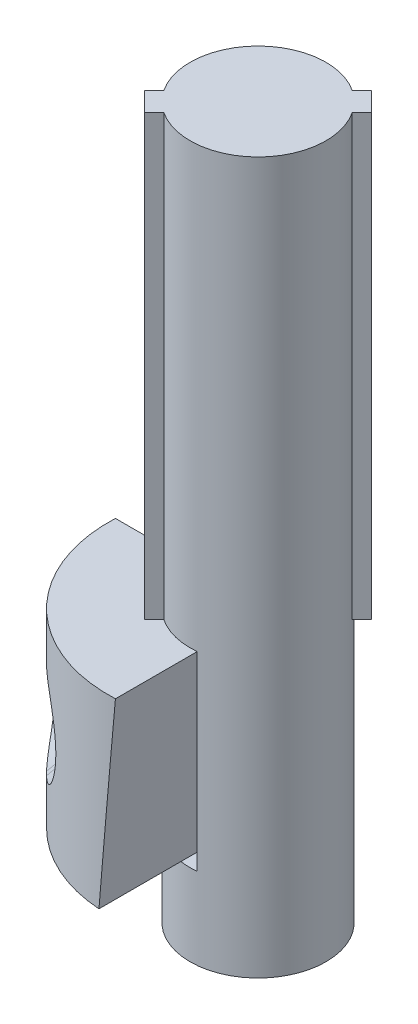
SolidWorks part; units mm, degrees
ref_plane "Front Plane" through (0, 0, 0) normal (0, 0, 1) x (1, 0, 0)
ref_plane "Top Plane" through (0, 0, 0) normal (0, 1, 0) x (1, 0, 0)
ref_plane "Right Plane" through (0, 0, 0) normal (1, 0, 0) x (0, 0, -1)
sketch "Sketch1" plane through (0, 0, 0) normal (0, 1, 0) x (1, 0, 0)
  line L0 (0, 12.1683) -> (0, -14.062) construction
  line L1 (-13.6994, 0) -> (17.366, 0) construction
  line L2 (0.0057, 5.75) -> (3.0125, 5.75)
  line L3 (5.75, 3.0125) -> (5.75, 0.0057)
  arc A0 (5.75, 0.0057) -> (0.0057, 5.75) centre (5.5, 5.5) cw
  arc A1 (5.75, 3.0125) -> (7.965, 5.0833) centre (5.5, 5.5) ccw
  arc A3 (5.0833, 7.965) -> (3.0125, 5.75) centre (5.5, 5.5) ccw
  arc A4 (5.75, 3.0125) -> (3.0125, 5.75) centre (5.5, 5.5) ccw
  dimension "D2" = 2.5
  dimension "D1" = 5.5
  dimension "D5" = 0.25
  dimension "D6" = 0.25
extrude "Boss-Extrude1" add sketch "Sketch1" along normal mid plane 30 contours A1 A4 A3 L2 A0 L3 region at (4.1706, 0, -4.1706)
sketch "Sketch2" plane through (0, 15, 0) normal (0, 1, 0) x (1, 0, 0)
  circle A0 centre (5.5, 5.5) radius 2.5
  circle A1 centre (5.5, 5.5) radius 5.5
  dimension "D1" = 11
  dimension "D2" = 5
extrude "Cut-Extrude1" cut sketch "Sketch2" against normal blind 20
sketch "Sketch3" plane through (0, -15, -15) normal (0, 1, 0) x (1, 0, 0)
  circle A1 centre (5.5, -9.5) radius 5.5
  circle A4 centre (5.5, -9.5) radius 2.5
  circle A5 centre (5.5, -9.5) radius 2.5 construction
  dimension "D1" = 11
extrude "Cut-Extrude2" cut sketch "Sketch3" along normal blind 3
ref_axis "Axis1" through (5.5, -5, -5.5) along (0, -1, 0)
ref_plane "Plane1" through (0, 0, -0.0057) normal (0, 0, 1) x (1, 0, 0)
ref_plane "Plane3" through (0.0057, 0, 0) normal (1, 0, 0) x (0, 0, -1)
sketch "Sketch5" plane through (0, 0, -0.0057) normal (0, 0, 1) x (1, 0, 0)
  line L0 (5.75, -5) -> (5.1376, -12)
  line L1 (5.1376, -12) -> (5.75, -12)
  line L2 (5.75, -12) -> (5.75, -5)
  dimension "D1" = 5
extrude "Cut-Extrude4" cut sketch "Sketch5" against normal blind 4 and the other way blind 0.25
sketch "Sketch10" plane through (0.0057, 0, 0) normal (1, 0, 0) x (0, 0, -1)
  line L0 (5.75, -12) -> (5.75, -5)
  line L1 (5.75, -5) -> (5.1376, -12)
  line L2 (5.1376, -12) -> (5.75, -12)
  dimension "D1" = 5
extrude "Cut-Extrude5" cut sketch "Sketch10" along normal blind 4 and the other way blind 2.5
ref_plane "Plane4" through (0, 15, 0) normal (0, 1, 0) x (1, 0, 0)
sketch "Sketch11" plane through (0, 15, 0) normal (0, 1, 0) x (1, 0, 0)
  circle A0 centre (5.5, 5.5) radius 2.5
  circle A1 centre (5.5, 5.5) radius 2.5 construction
extrude "Cut-Extrude6" cut sketch "Sketch11" against normal blind 3.85
sketch3d "3DSketch2"
  line L0 (1.6109, -5, -1.6109) -> (1.6109, -12, -1.6109)
  arc A0 (0.0057, -5, -5.75) -> (5.75, -5, -0.0057) centre (5.5, -5, -5.5) ccw construction
  arc A1 (0.012, -12, -5.1376) -> (5.1376, -12, -0.012) centre (5.5, -12, -5.5) ccw construction
  point P5 (5.5, 0.5, -5.5)
  point P9 (5.5, -6.5, -5.5)
  point P10 (1.6109, -8.5, -1.6109)
  point P11 (1.6109, -8.5, -1.6109)
sketch "Sketch4" plane through (0, 11.15, 0) normal (0, 1, 0) x (1, 0, 0)
  line L0 (8.743, 8.743) -> (1.3187, 1.3187) construction
  line L1 (-4.4, 0) -> (4.4, 0) construction
  line L2 (4.1215, 3.4144) -> (3.7679, 3.0608)
  line L3 (3.7679, 3.0608) -> (3.0608, 3.7679)
  line L4 (3.0608, 3.7679) -> (3.4144, 4.1215)
  line L5 (3.5346, 7.4654) -> (7.5363, 3.4637) construction
  line L6 (7.2321, 7.9392) -> (6.8785, 7.5856)
  line L7 (7.9392, 7.2321) -> (7.2321, 7.9392)
  line L8 (7.5856, 6.8785) -> (7.9392, 7.2321)
  circle A0 centre (5.5, 5.5) radius 2.5 construction
  arc A1 (3.4144, 4.1215) -> (4.1215, 3.4144) centre (5.5, 5.5) ccw
  arc A2 (6.8785, 7.5856) -> (7.5856, 6.8785) centre (5.5, 5.5) cw
  point P13 (3.9447, 3.2376)
  point P19 (0, 0)
  point P22 (0, 0)
  dimension "D3" = 0.5
  dimension "D1" = 45
  dimension "D2" = 1
extrude "Boss-Extrude2" add sketch "Sketch4" against normal up to surface (16.15 mm away) contours A1 L4 L3 L2 | L6 A2 L8 L7 region at (3.5794, 11.15, -3.5794) region at (7.4206, 11.15, -7.4206) up to face at (3.1506, -5, -3.1506)
ref_plane "Plane5" through (0.8688, 0, -0.8688) normal (-0.7071, 0, 0.7071) x (0.7071, 0, 0.7071)
hole_wizard "CSK SLOT for M1.6 Countersunk Flat Head Screw3" positions "Sketch14" profile "Sketch15" size "M1.6" standard "ISO" slot yes
sketch "Sketch14" plane through (0.8688, 0, -0.8688) normal (-0.7071, 0, 0.7071) x (0.7071, 0, 0.7071)
  line L0 (-1, -8.5) -> (1, -8.5) construction
  point P0 (0, -8.5)
sketch "Sketch15" plane through (0.8688, -8.5, -0.8688) normal (0, 1, 0) x (0.7071, 0, 0.7071)
  line L0 (0, 0) -> (0, 6.5408)
  line L1 (0, 6.5408) -> (0.9, 6)
  line L2 (0.9, 6) -> (0.9, 1.9)
  line L3 (0.9, 1.9) -> (1.8, 1)
  line L4 (1.8, 1) -> (1.8, 0)
  line L6 (1.8, 0) -> (0, 0)
  line L7 (-0.9, 1.9) -> (-1.8, 1) construction
  line L10 (0, 6.5408) -> (-0.9, 6) construction
  line L11 (0, -6.35) -> (0, 107.95) construction
  dimension "Hole Dia." = 1.8
  dimension "Hole Depth" = 6
  dimension "C'Sink Dia." = 3.6
  dimension "C'Sink Angle" = 90
  dimension "Drill Angle" = 118
  dimension "Head Clearance" = 1
